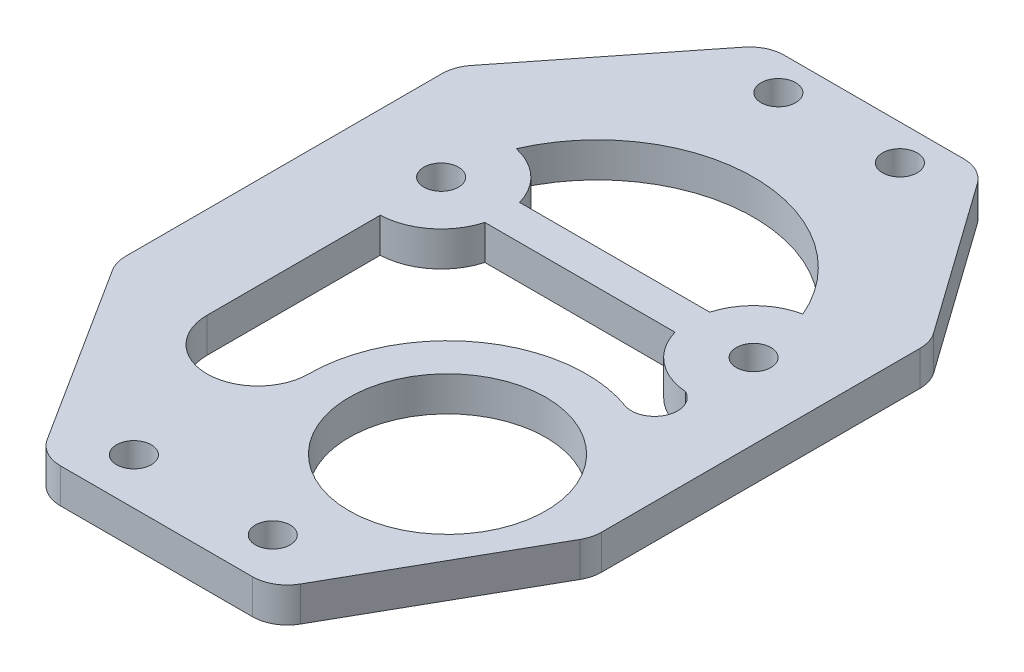
SolidWorks part; units mm, degrees
note: The reader was unsure of these and kept them because the rebuilt part matched: thickness of "Base-Flange1", "Sheet-Metal1", "Sheet-Metal2".
ref_plane "Front Plane" through (0, 0, 0) normal (0, 0, 1) x (1, 0, 0)
ref_plane "Top Plane" through (0, 0, 0) normal (0, 1, 0) x (1, 0, 0)
ref_plane "Right Plane" through (0, 0, 0) normal (1, 0, 0) x (0, 0, -1)
sketch "Sketch1" plane through (0, 0, 0) normal (0, 1, 0) x (1, 0, 0)
  line L0 (0, 34.5262) -> (0, -34.5262) construction
  line L1 (-42.1133, 0) -> (42.1133, 0) construction
  line L2 (19.6094, -14.0594) -> (10.8621, -29.4802)
  line L3 (-7.7982, 31) -> (7.7021, 31)
  line L5 (-8.3526, -31) -> (8.2527, -31)
  line L6 (20, 14.9247) -> (20, -12.5792)
  line L7 (13.5, 7.05) -> (-13.5, 7.05) construction
  line L8 (10.147, 29.7386) -> (19.4449, 16.6633)
  line L9 (-13.2814, 0) -> (-13.2814, 1.568)
  line L10 (-8.2227, 8.55) -> (8.2085, 8.55)
  line L11 (-20.564, 16.7008) -> (-10.1508, 29.8615)
  line L12 (-21.2114, 14.8393) -> (-21.2114, -12.4977)
  line L13 (-13.2814, -13.4) -> (-13.2814, 0)
  line L14 (-20.7429, -14.1076) -> (-10.884, -29.6099)
  line L15 (-8.2227, 5.55) -> (8.2085, 5.55)
  circle A0 centre (7.5, -13.4) radius 8.5
  circle A1 centre (6, -27) radius 1.5
  circle A2 centre (-6, -27) radius 1.5
  arc A3 (11.6553, -2.1424) -> (13.1131, 1.5636) centre (12.21, -0.2209) ccw
  arc A4 (11.6553, -2.1424) -> (-4.5, -13.4) centre (7.5, -13.4) ccw
  arc A5 (-13.2814, -13.4) -> (-4.5, -13.4) centre (-8.8907, -13.4) ccw
  circle A6 centre (5.25, 27.9408) radius 1.5
  circle A7 centre (-5.25, 27.9408) radius 1.5
  circle A8 centre (13.5, 7.05) radius 1.5
  arc A9 (12.3796, 12.4347) -> (8.2085, 8.55) centre (13.5, 7.05) ccw
  arc A11 (12.3796, 12.4347) -> (-12.3852, 12.4219) centre (0, 7.05) ccw
  circle A12 centre (-13.5, 7.05) radius 1.5
  arc A13 (-13.2814, 1.568) -> (-8.2227, 5.55) centre (-13.5, 7.05) ccw
  arc A14 (-10.1508, 29.8615) -> (-7.7982, 31) centre (-7.7982, 28) cw
  arc A15 (-21.2114, -12.4977) -> (-20.7429, -14.1076) centre (-18.2114, -12.4977) ccw
  arc A16 (-21.2114, 14.8393) -> (-20.564, 16.7008) centre (-18.2114, 14.8393) cw
  arc A17 (-10.884, -29.6099) -> (-8.3526, -31) centre (-8.3526, -28) ccw
  arc A18 (10.8621, -29.4802) -> (8.2527, -31) centre (8.2527, -28) cw
  arc A19 (19.6094, -14.0594) -> (20, -12.5792) centre (17, -12.5792) ccw
  arc A20 (19.4449, 16.6633) -> (20, 14.9247) centre (17, 14.9247) cw
  arc A21 (10.147, 29.7386) -> (7.7021, 31) centre (7.7021, 28) ccw
  arc A22 (-8.2227, 8.55) -> (-12.3852, 12.4219) centre (-13.5, 7.05) ccw
  arc A23 (8.2085, 5.55) -> (13.1131, 1.5636) centre (13.5, 7.05) ccw
  point P0 (0, 0)
  point P4 (0, 0)
  point P8 (0, 0)
  point P36 (-9.25, 31)
  point P50 (-10, -31)
  point P53 (10, -31)
  point P56 (20, -13.3709)
  point P61 (9.25, 31)
  dimension "D2" = 17.6
  dimension "D4" = 17
  dimension "D5" = 4
  dimension "D9" = 62
  dimension "D10" = 20.45
  dimension "D12" = 13.15
  dimension "D14" = 4
  dimension "D15" = 12
  dimension "D16" = 10.5
  dimension "D18" = 3
  dimension "D19" = 13.5
  dimension "D20" = 11
  dimension "D22" = 4
  dimension "D24" = 3
  dimension "D25" = 3
  dimension "D3" = 7.5
  dimension "D6" = 4
  dimension "D7" = 6
  dimension "D8" = 12
  dimension "D11" = 4
  dimension "D13" = 4.71
  dimension "D17" = 5.25
  dimension "D21" = 7.93
  dimension "D23" = 6.5
base flange "Base-Flange1" sketch "Sketch1" thickness 3 reverse thickness direction yes parameters "D1"=0.7366
scale "Scale1" scale about centroid uniform scaling yes scale factor 1.8
sketch "Bend-Lines1" [suppressed] plane through (0, 0, 0) normal (0, 1, 0) x (1, 0, 0)
sketch "Bounding-Box1" [suppressed] plane through (0, 0, 0) normal (0, 1, 0) x (1, 0, 0)
sheet metal parameters "Sheet-Metal1" thickness 3 parameters "D1"=0.7366
flat pattern "Flat-Pattern1" [suppressed]
sketch "Bend-Lines2" plane through (0, 0, 0) normal (0, 1, 0) x (1, 0, 0)
sketch3d "Bounding-Box2" [suppressed]
  line L0 (13.4132, -59, 0) -> (13.4132, 3, 0) construction
  line L1 (-27.7982, -59, 0) -> (-27.7982, 3, 0) construction
  line L2 (13.4132, -59, 0) -> (-27.7982, -59, 0) construction
  line L3 (13.4132, 3, 0) -> (-27.7982, 3, 0) construction
sheet metal parameters "Sheet-Metal2" thickness 3 parameters "D1"=0.7366
flat pattern "Flat-Pattern1"
sketch "Bend-Lines2" plane through (0, 0, 0) normal (0, 1, 0) x (1, 0, 0)
sketch3d "Bounding-Box2" [suppressed]
  line L0 (13.4132, -59, 0) -> (13.4132, 3, 0) construction
  line L1 (-27.7982, -59, 0) -> (-27.7982, 3, 0) construction
  line L2 (13.4132, -59, 0) -> (-27.7982, -59, 0) construction
  line L3 (13.4132, 3, 0) -> (-27.7982, 3, 0) construction
